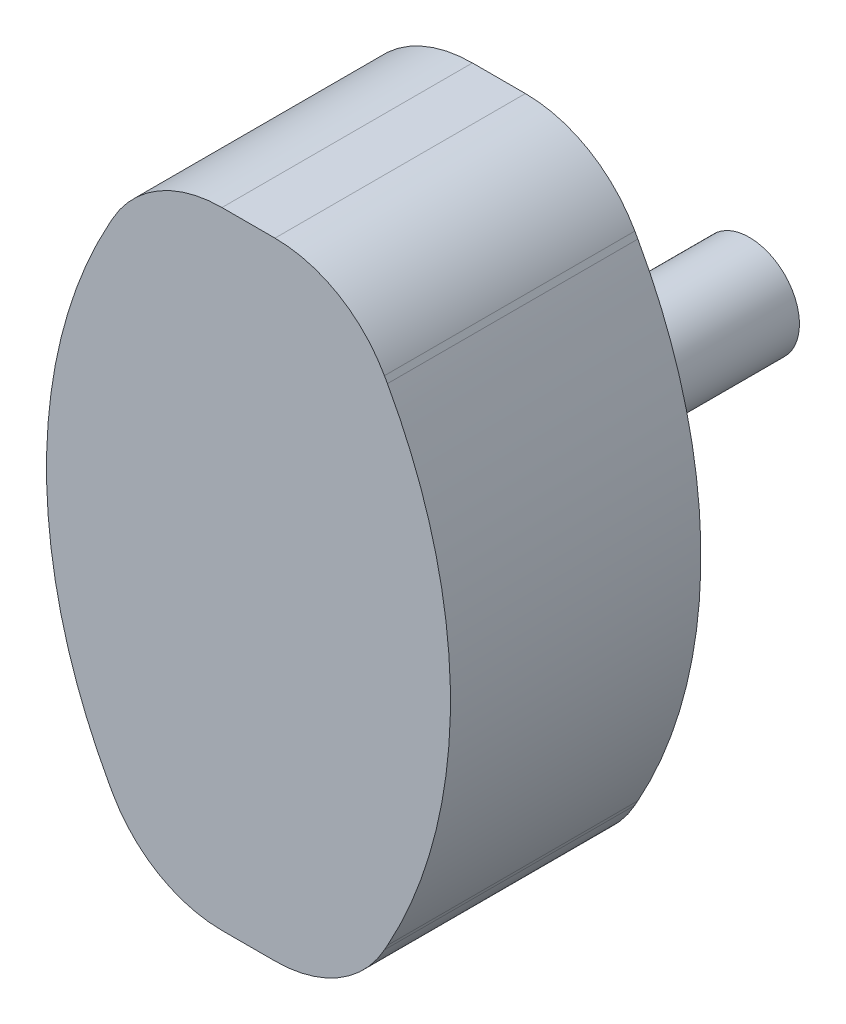
SolidWorks part; units mm, degrees
ref_plane "Plano frontal" through (0, 0, 0) normal (0, 0, 1) x (1, 0, 0)
ref_plane "Plano superior" through (0, 0, 0) normal (0, 1, 0) x (1, 0, 0)
ref_plane "Plano direito" through (0, 0, 0) normal (1, 0, 0) x (0, 0, -1)
sketch "Esboço1" plane through (0, 0, 0) normal (0, 0, 1) x (1, 0, 0)
  line L0 (-18.7013, 0) -> (8.282, 0) construction
  line L1 (0, 19.102) -> (0, -8.9499) construction
  line L2 (5.5484, -9.7129) -> (4, -12.5)
  line L3 (4, -12.5) -> (0, -12.5)
  line L4 (-4, -12.5) -> (0, -12.5)
  line L5 (-5.5484, -9.7129) -> (-4, -12.5)
  line L6 (5.5484, 9.7129) -> (4, 12.5)
  line L7 (4, 12.5) -> (0, 12.5)
  line L8 (-4, 12.5) -> (0, 12.5)
  line L9 (-5.5484, 9.7129) -> (-4, 12.5)
  arc A0 (5.5484, 9.7129) -> (5.5484, -9.7129) centre (-11.9347, 0) cw
  arc A1 (-5.5484, 9.7129) -> (-5.5484, -9.7129) centre (11.9347, 0) ccw
  point P3 (0, 0)
  point P15 (0, 0)
  point P16 (0, 0)
  point P20 (38.1147, -38.8514)
  point P21 (36.3339, 36.2764)
  point P22 (0, 0)
  dimension "D1" = 20
  dimension "D2" = 4
  dimension "D3" = 25
extrude "Ressalto-extrusão1" add sketch "Esboço1" along normal blind 10
sketch "Esboço2" plane through (0, 0, 0) normal (0, 0, -1) x (-1, 0, 0)
  circle A0 centre (0, 0) radius 2
  dimension "D1" = 4
extrude "Ressalto-extrusão2" add sketch "Esboço2" along normal blind 10
fillet "Filete1" radius 5 4 edges at (-4, 12.5, 5) (4, 12.5, 5) (-4, -12.5, 5) (4, -12.5, 5)
fillet "Filete2" radius 2 1 edges at (-2, 0, 0)
